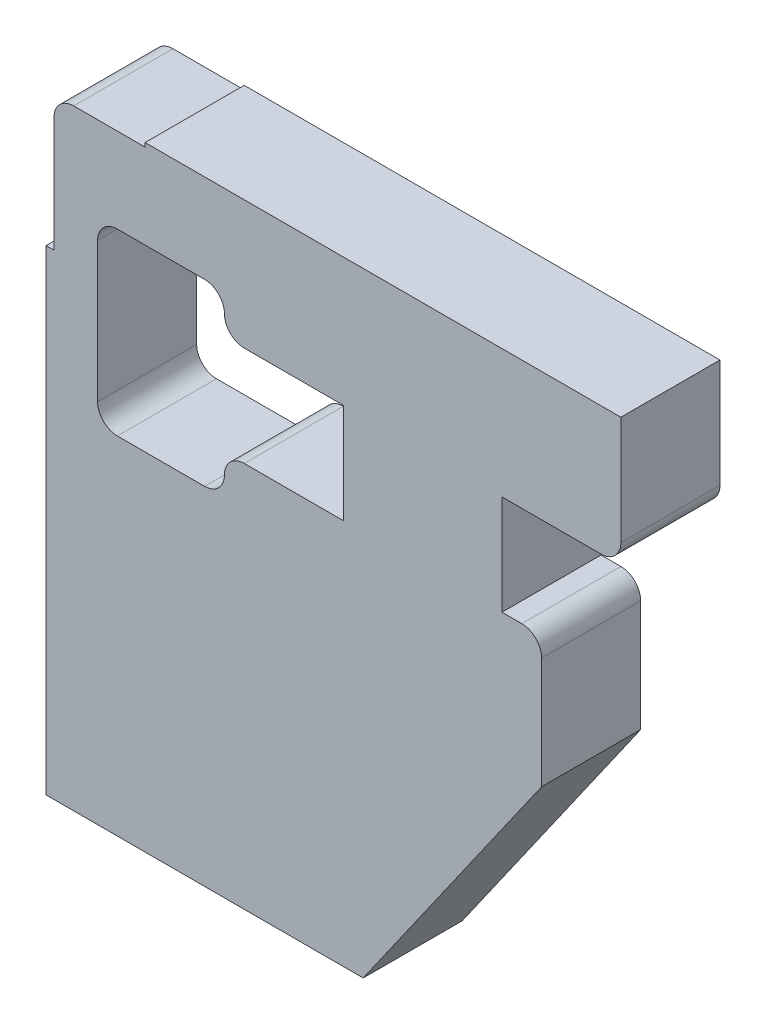
SolidWorks part; units mm, degrees
material "PBT General Purpose"
ref_plane "Front Plane" through (0, 0, 0) normal (0, 0, 1) x (1, 0, 0)
ref_plane "Top Plane" through (0, 0, 0) normal (0, 1, 0) x (1, 0, 0)
ref_plane "Right Plane" through (0, 0, 0) normal (1, 0, 0) x (0, 0, -1)
sketch "frame_outline" plane through (0, 0, 0) normal (0, 0, 1) x (1, 0, 0)
  line L0 (0, 0) -> (0, -0.4) construction
  line L1 (0, 0) -> (0.3, 0) construction
  line L2 (0, -0.4) -> (0.05, -0.4) construction
  line L3 (0.3, 0) -> (0.3, -0.05) construction
  line L8 (0.3, -0.05) -> (1.5, -0.05)
  line L19 (0.3, -0.05) -> (0.3, -0.06)
  line L20 (0.3, -0.06) -> (0.07, -0.06)
  line L21 (0.07, -0.06) -> (0.07, -0.4)
  line L62 (0.05, -0.4) -> (0.07, -0.4)
  line L63 (0.05, -0.4) -> (0.05, -1.6)
  line L64 (0.05, -1.6) -> (0.85, -1.6)
  line L65 (0.85, -1.6) -> (1.3, -0.9573)
  line L66 (1.3, -0.9573) -> (1.3, -0.626)
  line L67 (1.3, -0.626) -> (1.2, -0.626)
  line L68 (1.2, -0.626) -> (1.2, -0.374)
  line L69 (1.2, -0.374) -> (1.5, -0.374)
  line L70 (1.5, -0.374) -> (1.5, -0.05)
  line L71 (0, -0.5) -> (1.8135, -0.5) construction
  line L72 (0.5, -0.374) -> (0.8, -0.374)
  line L73 (0.8, -0.374) -> (0.8, -0.626)
  line L74 (0.8, -0.626) -> (0.5, -0.626)
  line L75 (0.5, -0.626) -> (0.5, -0.726)
  line L76 (0.5, -0.726) -> (0.18, -0.726)
  line L77 (0.18, -0.726) -> (0.18, -0.274)
  line L78 (0.18, -0.274) -> (0.5, -0.274)
  line L79 (0.5, -0.274) -> (0.5, -0.374)
  line L80 (1.2, -0.05) -> (1.2, -1.1001) construction
  line L81 (0.8, -0.374) -> (1.2, -0.374) construction
  point P22 (1.2, -0.5)
  point P32 (1, -0.374)
  point P33 (1.3, -0.7917)
  dimension "D2" = 0.3
  dimension "D6" = 1.2
  dimension "D4" = 0.05
  dimension "D1" = 0.05
  dimension "D3" = 0.4
  dimension "D5" = 0.02
  dimension "D7" = 0.01
  dimension "D8" = 1.2
  dimension "D9" = 0.5
  dimension "D10" = 0.252
  dimension "D11" = 0.1
  dimension "D12" = 0.32
  dimension "D13" = 0.3
  dimension "D15" = 0.4
  dimension "D16" = 0.85
  dimension "D18" = 1
  dimension "D17" = 55
  dimension "D14" = 0.3
  dimension "D19" = 0.1
  dimension "D20" = 1.0501
extrude "Boss-Extrude1" add sketch "frame_outline" along normal mid plane 0.25
fillet "Fillet1" radius 0.05 9 edges at (1.3, -0.626, 0) (1.5, -0.374, 0) (0.5, -0.374, 0) (0.5, -0.626, 0) (0.5, -0.726, 0) (0.18, -0.726, 0) (0.5, -0.274, 0) (0.18, -0.274, 0) (0.07, -0.06, 0)
equation "\"t\"= 0.25'thickness of the sheets"
equation "\"t_cf\"= 0.115'thickness of single carbon fiber layer"
equation "\"t_kapton\"= 0.025'thickness of single Kapton flex layer"
equation "\"t_fr4\"= 0.1'thickness of FR4 with copper layer"
equation "\"joint_flex\"= 0.1'Width of flextures gap"
equation "\"joint_flex_eff\"= 0.02'Width of flecture after castelation"
equation "\"joint_fold\"= 0.2'Width of folding joints for 90deg fold"
equation "\"gap_tolerance\"= 0.002'Width to have interfecence fit between carbon fiber inserts"
equation "\"assemble_angle\"= 90'Angle of assembly parts"
equation "\"D1@Boss-Extrude1\"=\"t\""
equation "\"D4@frame_outline\"=\"joint_flex\"/2"
equation "\"D1@frame_outline\"=\"joint_flex\"/2"
equation "\"D10@frame_outline\"=\"t\"+\"gap_tolerance\""
equation "\"D9@frame_outline\"=\"link_lift\""
equation "\"link_lift\"= 0.5'Actuation linkage amplification for the lift motion"
equation "\"link_swing\"= 0.45'Actuation linkage amplification for the swing motion"
